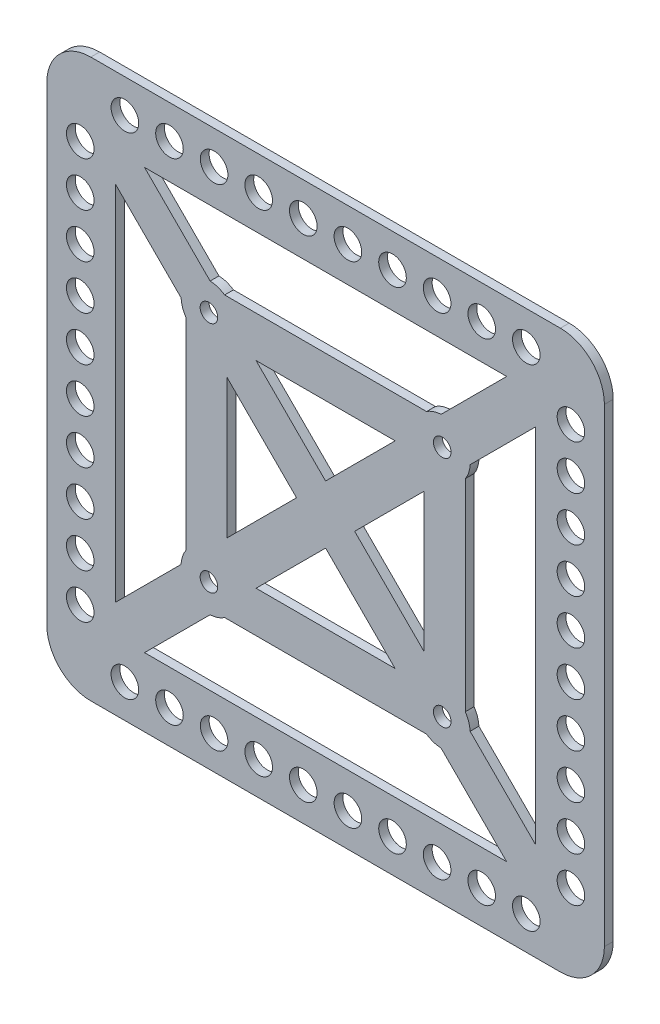
SolidWorks part; units mm, degrees
ref_plane "Front Plane" through (0, 0, 0) normal (0, 0, 1) x (1, 0, 0)
ref_plane "Top Plane" through (0, 0, 0) normal (0, 1, 0) x (1, 0, 0)
ref_plane "Right Plane" through (0, 0, 0) normal (1, 0, 0) x (0, 0, -1)
sketch "Sketch1" plane through (0, 0, 0) normal (0, 0, 1) x (1, 0, 0)
  line L0 (453.6808, -1249.6067) -> (438.4808, -1249.6067) construction
  line L1 (467.0808, -1278.2067) -> (577.0808, -1278.2067) construction
  line L2 (467.0808, -1278.2067) -> (467.0808, -1388.2067) construction
  line L3 (467.0808, -1388.2067) -> (577.0808, -1388.2067) construction
  line L4 (577.0808, -1278.2067) -> (577.0808, -1388.2067) construction
  line L5 (438.4808, -1264.8067) -> (438.4808, -1401.6067) construction
  line L6 (453.6808, -1249.6067) -> (590.4808, -1249.6067) construction
  line L7 (467.0808, -1388.2067) -> (577.0808, -1278.2067) construction
  line L8 (605.6808, -1401.6067) -> (605.6808, -1264.8067) construction
  line L9 (590.4808, -1416.8067) -> (453.6808, -1416.8067) construction
  line L10 (605.6808, -1401.6067) -> (605.6808, -1416.8067) construction
  line L12 (427.0808, -1238.2067) -> (617.0808, -1238.2067) construction
  line L13 (427.0808, -1238.2067) -> (427.0808, -1428.2067) construction
  line L14 (427.0808, -1428.2067) -> (617.0808, -1428.2067) construction
  line L15 (617.0808, -1238.2067) -> (617.0808, -1428.2067) construction
  line L16 (427.0808, -1238.2067) -> (617.0808, -1428.2067) construction
  line L17 (427.0808, -1428.2067) -> (617.0808, -1238.2067) construction
  circle A0 centre (453.6808, -1249.6067) radius 4.7
  circle A1 centre (453.6808, -1249.6067) radius 5.7
  circle A2 centre (468.8808, -1249.6067) radius 4.7
  circle A3 centre (468.8808, -1249.6067) radius 5.7
  circle A4 centre (484.0808, -1249.6067) radius 4.7
  circle A5 centre (484.0808, -1249.6067) radius 5.7
  circle A6 centre (499.2808, -1249.6067) radius 4.7
  circle A7 centre (499.2808, -1249.6067) radius 5.7
  circle A8 centre (514.4808, -1249.6067) radius 4.7
  circle A9 centre (514.4808, -1249.6067) radius 5.7
  circle A10 centre (529.6808, -1249.6067) radius 4.7
  circle A11 centre (529.6808, -1249.6067) radius 5.7
  circle A12 centre (544.8808, -1249.6067) radius 4.7
  circle A13 centre (544.8808, -1249.6067) radius 5.7
  circle A14 centre (560.0808, -1249.6067) radius 4.7
  circle A15 centre (560.0808, -1249.6067) radius 5.7
  circle A16 centre (575.2808, -1249.6067) radius 4.7
  circle A17 centre (575.2808, -1249.6067) radius 5.7
  circle A18 centre (590.4808, -1249.6067) radius 4.7
  circle A19 centre (590.4808, -1249.6067) radius 5.7
  circle A20 centre (438.4808, -1249.6067) radius 4.7 construction
  circle A21 centre (438.4808, -1249.6067) radius 5.7 construction
  circle A22 centre (438.4808, -1264.8067) radius 4.7
  circle A23 centre (438.4808, -1264.8067) radius 5.7
  circle A24 centre (438.4808, -1280.0067) radius 4.7
  circle A25 centre (438.4808, -1280.0067) radius 5.7
  circle A26 centre (438.4808, -1295.2067) radius 4.7
  circle A27 centre (438.4808, -1295.2067) radius 5.7
  circle A28 centre (438.4808, -1310.4067) radius 4.7
  circle A29 centre (438.4808, -1310.4067) radius 5.7
  circle A30 centre (438.4808, -1325.6067) radius 4.7
  circle A31 centre (438.4808, -1325.6067) radius 5.7
  circle A32 centre (438.4808, -1340.8067) radius 4.7
  circle A33 centre (438.4808, -1340.8067) radius 5.7
  circle A34 centre (438.4808, -1356.0067) radius 4.7
  circle A35 centre (438.4808, -1356.0067) radius 5.7
  circle A36 centre (438.4808, -1371.2067) radius 4.7
  circle A37 centre (438.4808, -1371.2067) radius 5.7
  circle A38 centre (438.4808, -1386.4067) radius 4.7
  circle A39 centre (438.4808, -1386.4067) radius 5.7
  circle A40 centre (438.4808, -1401.6067) radius 4.7
  circle A41 centre (438.4808, -1401.6067) radius 5.7
  circle A42 centre (605.6808, -1416.8067) radius 5.7 construction
  circle A43 centre (605.6808, -1416.8067) radius 4.7 construction
  circle A44 centre (453.6808, -1416.8067) radius 5.7
  circle A45 centre (453.6808, -1416.8067) radius 4.7
  circle A46 centre (468.8808, -1416.8067) radius 5.7
  circle A47 centre (468.8808, -1416.8067) radius 4.7
  circle A48 centre (484.0808, -1416.8067) radius 5.7
  circle A49 centre (484.0808, -1416.8067) radius 4.7
  circle A50 centre (499.2808, -1416.8067) radius 5.7
  circle A51 centre (499.2808, -1416.8067) radius 4.7
  circle A52 centre (514.4808, -1416.8067) radius 5.7
  circle A53 centre (514.4808, -1416.8067) radius 4.7
  circle A54 centre (529.6808, -1416.8067) radius 5.7
  circle A55 centre (529.6808, -1416.8067) radius 4.7
  circle A56 centre (544.8808, -1416.8067) radius 5.7
  circle A57 centre (544.8808, -1416.8067) radius 4.7
  circle A58 centre (560.0808, -1416.8067) radius 5.7
  circle A59 centre (560.0808, -1416.8067) radius 4.7
  circle A60 centre (575.2808, -1416.8067) radius 5.7
  circle A61 centre (575.2808, -1416.8067) radius 4.7
  circle A62 centre (590.4808, -1416.8067) radius 5.7
  circle A63 centre (590.4808, -1416.8067) radius 4.7
  circle A64 centre (605.6808, -1264.8067) radius 5.7
  circle A65 centre (605.6808, -1264.8067) radius 4.7
  circle A66 centre (605.6808, -1280.0067) radius 5.7
  circle A67 centre (605.6808, -1280.0067) radius 4.7
  circle A68 centre (605.6808, -1295.2067) radius 5.7
  circle A69 centre (605.6808, -1295.2067) radius 4.7
  circle A70 centre (605.6808, -1310.4067) radius 5.7
  circle A71 centre (605.6808, -1310.4067) radius 4.7
  circle A72 centre (605.6808, -1325.6067) radius 5.7
  circle A73 centre (605.6808, -1325.6067) radius 4.7
  circle A74 centre (605.6808, -1340.8067) radius 5.7
  circle A75 centre (605.6808, -1340.8067) radius 4.7
  circle A76 centre (605.6808, -1356.0067) radius 5.7
  circle A77 centre (605.6808, -1356.0067) radius 4.7
  circle A78 centre (605.6808, -1371.2067) radius 5.7
  circle A79 centre (605.6808, -1371.2067) radius 4.7
  circle A80 centre (605.6808, -1386.4067) radius 5.7
  circle A81 centre (605.6808, -1386.4067) radius 4.7
  circle A82 centre (605.6808, -1401.6067) radius 5.7
  circle A83 centre (605.6808, -1401.6067) radius 4.7
  point P4 (522.0808, -1249.6067)
  point P5 (522.0808, -1278.2067)
  point P10 (438.4808, -1333.2067)
  point P42 (467.0808, -1333.2067)
  point P136 (522.0808, -1333.2067)
  dimension "D5" = 9.4
  dimension "D6" = 1
  dimension "D1" = 110
  dimension "D2" = 110
  dimension "D3" = 190
  dimension "D4" = 136.8
  dimension "D8" = 11
  dimension "D9" = 136.8
  dimension "D10" = 190
  dimension "D7" = 10
extrude "Boss-Extrude1" add sketch "Sketch1" along normal blind 16
sketch "Sketch4" plane through (0, 0, 0) normal (0, 0, 1) x (1, 0, 0)
  line L0 (427.0808, -1238.2067) -> (617.0808, -1428.2067) construction
  line L1 (427.0808, -1428.2067) -> (617.0808, -1428.2067)
  line L2 (427.0808, -1428.2067) -> (427.0808, -1238.2067)
  line L3 (427.0808, -1238.2067) -> (617.0808, -1238.2067)
  line L4 (617.0808, -1428.2067) -> (617.0808, -1238.2067)
  line L5 (427.0808, -1428.2067) -> (617.0808, -1238.2067) construction
  line L6 (427.0808, -1238.2067) -> (617.0808, -1428.2067) construction
  circle A0 centre (438.4808, -1264.8067) radius 4.7 construction
  circle A1 centre (438.4808, -1280.0067) radius 4.7 construction
  circle A2 centre (438.4808, -1295.2067) radius 4.7 construction
  circle A3 centre (438.4808, -1310.4067) radius 4.7 construction
  circle A4 centre (438.4808, -1325.6067) radius 4.7 construction
  circle A5 centre (438.4808, -1340.8067) radius 4.7 construction
  circle A6 centre (438.4808, -1356.0067) radius 4.7 construction
  circle A7 centre (438.4808, -1371.2067) radius 4.7 construction
  circle A8 centre (438.4808, -1386.4067) radius 4.7 construction
  circle A9 centre (438.4808, -1401.6067) radius 4.7 construction
  circle A10 centre (453.6808, -1416.8067) radius 4.7 construction
  circle A11 centre (468.8808, -1416.8067) radius 4.7 construction
  circle A12 centre (484.0808, -1416.8067) radius 4.7 construction
  circle A13 centre (499.2808, -1416.8067) radius 4.7 construction
  circle A14 centre (514.4808, -1416.8067) radius 4.7 construction
  circle A15 centre (529.6808, -1416.8067) radius 4.7 construction
  circle A16 centre (544.8808, -1416.8067) radius 4.7 construction
  circle A17 centre (560.0808, -1416.8067) radius 4.7 construction
  circle A18 centre (575.2808, -1416.8067) radius 4.7 construction
  circle A19 centre (590.4808, -1416.8067) radius 4.7 construction
  circle A20 centre (605.6808, -1401.6067) radius 4.7 construction
  circle A21 centre (605.6808, -1386.4067) radius 4.7 construction
  circle A22 centre (605.6808, -1371.2067) radius 4.7 construction
  circle A23 centre (605.6808, -1356.0067) radius 4.7 construction
  circle A24 centre (605.6808, -1340.8067) radius 4.7 construction
  circle A25 centre (605.6808, -1325.6067) radius 4.7 construction
  circle A26 centre (605.6808, -1310.4067) radius 4.7 construction
  circle A27 centre (605.6808, -1295.2067) radius 4.7 construction
  circle A28 centre (605.6808, -1280.0067) radius 4.7 construction
  circle A29 centre (605.6808, -1264.8067) radius 4.7 construction
  circle A30 centre (590.4808, -1249.6067) radius 4.7 construction
  circle A31 centre (575.2808, -1249.6067) radius 4.7 construction
  circle A32 centre (560.0808, -1249.6067) radius 4.7 construction
  circle A33 centre (544.8808, -1249.6067) radius 4.7 construction
  circle A34 centre (529.6808, -1249.6067) radius 4.7 construction
  circle A35 centre (514.4808, -1249.6067) radius 4.7 construction
  circle A36 centre (499.2808, -1249.6067) radius 4.7 construction
  circle A37 centre (484.0808, -1249.6067) radius 4.7 construction
  circle A38 centre (468.8808, -1249.6067) radius 4.7 construction
  circle A39 centre (453.6808, -1249.6067) radius 4.7 construction
  circle A40 centre (438.4808, -1264.8067) radius 4.7
  circle A41 centre (438.4808, -1280.0067) radius 4.7
  circle A42 centre (438.4808, -1295.2067) radius 4.7
  circle A43 centre (438.4808, -1310.4067) radius 4.7
  circle A44 centre (438.4808, -1325.6067) radius 4.7
  circle A45 centre (438.4808, -1340.8067) radius 4.7
  circle A46 centre (438.4808, -1356.0067) radius 4.7
  circle A47 centre (438.4808, -1371.2067) radius 4.7
  circle A48 centre (438.4808, -1386.4067) radius 4.7
  circle A49 centre (438.4808, -1401.6067) radius 4.7
  circle A50 centre (453.6808, -1416.8067) radius 4.7
  circle A51 centre (468.8808, -1416.8067) radius 4.7
  circle A52 centre (484.0808, -1416.8067) radius 4.7
  circle A53 centre (499.2808, -1416.8067) radius 4.7
  circle A54 centre (514.4808, -1416.8067) radius 4.7
  circle A55 centre (529.6808, -1416.8067) radius 4.7
  circle A56 centre (544.8808, -1416.8067) radius 4.7
  circle A57 centre (560.0808, -1416.8067) radius 4.7
  circle A58 centre (575.2808, -1416.8067) radius 4.7
  circle A59 centre (590.4808, -1416.8067) radius 4.7
  circle A60 centre (605.6808, -1401.6067) radius 4.7
  circle A61 centre (605.6808, -1386.4067) radius 4.7
  circle A62 centre (605.6808, -1371.2067) radius 4.7
  circle A63 centre (605.6808, -1356.0067) radius 4.7
  circle A64 centre (605.6808, -1340.8067) radius 4.7
  circle A65 centre (605.6808, -1325.6067) radius 4.7
  circle A66 centre (605.6808, -1310.4067) radius 4.7
  circle A67 centre (605.6808, -1295.2067) radius 4.7
  circle A68 centre (605.6808, -1280.0067) radius 4.7
  circle A69 centre (605.6808, -1264.8067) radius 4.7
  circle A70 centre (590.4808, -1249.6067) radius 4.7
  circle A71 centre (575.2808, -1249.6067) radius 4.7
  circle A72 centre (560.0808, -1249.6067) radius 4.7
  circle A73 centre (544.8808, -1249.6067) radius 4.7
  circle A74 centre (529.6808, -1249.6067) radius 4.7
  circle A75 centre (514.4808, -1249.6067) radius 4.7
  circle A76 centre (499.2808, -1249.6067) radius 4.7
  circle A77 centre (484.0808, -1249.6067) radius 4.7
  circle A78 centre (468.8808, -1249.6067) radius 4.7
  circle A79 centre (453.6808, -1249.6067) radius 4.7
  point P0 (522.0808, -1333.2067)
extrude "Boss-Extrude3" add sketch "Sketch4" against normal blind 6
sketch "Sketch5" plane through (0, 0, 0) normal (0, 0, 1) x (1, 0, 0)
  circle A0 centre (482.3308, -1293.4567) radius 3
  circle A1 centre (561.8308, -1293.4567) radius 3
  circle A2 centre (561.8308, -1372.9567) radius 3
  circle A3 centre (482.3308, -1372.9567) radius 3
  point P11 (522.0808, -1333.2067)
  dimension "D1" = 6
  dimension "D2" = 4
extrude "Cut-Extrude1" cut sketch "Sketch5" against normal blind 6
sketch "Sketch7" plane through (0, 0, -6) normal (0, 0, -1) x (-1, 0, 0)
  line L6 (-617.0808, -1238.2067) -> (-427.0808, -1428.2067) construction
  line L7 (-617.0808, -1428.2067) -> (-427.0808, -1238.2067) construction
  line L8 (-612.1311, -1433.1565) -> (-422.1311, -1243.1565)
  line L9 (-450.4808, -1404.8067) -> (-593.6808, -1404.8067)
  line L10 (-450.4808, -1404.8067) -> (-450.4808, -1261.6067)
  line L11 (-450.4808, -1261.6067) -> (-593.6808, -1261.6067)
  line L12 (-593.6808, -1404.8067) -> (-593.6808, -1261.6067)
  line L13 (-450.4808, -1404.8067) -> (-593.6808, -1261.6067) construction
  line L14 (-450.4808, -1261.6067) -> (-593.6808, -1404.8067) construction
  line L15 (-474.4808, -1380.8067) -> (-569.6808, -1380.8067)
  line L16 (-474.4808, -1380.8067) -> (-474.4808, -1285.6067)
  line L17 (-474.4808, -1285.6067) -> (-569.6808, -1285.6067)
  line L18 (-569.6808, -1380.8067) -> (-569.6808, -1285.6067)
  line L19 (-474.4808, -1380.8067) -> (-569.6808, -1285.6067) construction
  line L20 (-474.4808, -1285.6067) -> (-569.6808, -1380.8067) construction
  line L21 (-622.0306, -1243.1565) -> (-432.0306, -1433.1565)
  line L22 (-622.0306, -1423.257) -> (-432.0306, -1233.257)
  line L23 (-612.1311, -1233.257) -> (-422.1311, -1423.257)
  line L24 (-467.0808, -1388.2067) -> (-577.0808, -1278.2067) construction
  line L26 (-488.4808, -1366.8067) -> (-555.6808, -1366.8067)
  line L27 (-488.4808, -1366.8067) -> (-488.4808, -1299.6067)
  line L28 (-488.4808, -1299.6067) -> (-555.6808, -1299.6067)
  line L29 (-555.6808, -1366.8067) -> (-555.6808, -1299.6067)
  line L30 (-488.4808, -1366.8067) -> (-555.6808, -1299.6067) construction
  line L31 (-488.4808, -1299.6067) -> (-555.6808, -1366.8067) construction
  circle A0 centre (-605.6808, -1401.6067) radius 5.7 construction
  point P4 (-522.0808, -1333.2067)
  point P18 (-522.0808, -1333.2067)
  point P37 (-522.0808, -1333.2067)
  dimension "D1" = 12
  dimension "D2" = 12
  dimension "D3" = 12
  dimension "D6" = 14
  dimension "D7" = 24
  dimension "D4" = 7
  dimension "D5" = 7
extrude "Cut-Extrude2" cut sketch "Sketch7" against normal blind 6 contours L11 L23 L17 L22 | L22 L28 L23 | L29 L22 L21 | L26 L21 L8 | L23 L27 L8 | L16 L23 L10 L8 | L21 L15 L8 L9 | L12 L22 L18 L21 region at (522.0808, -1393.7725, -6) region at (522.0808, -1358.9066, -6) region at (582.6466, -1333.2067, -6) region at (461.5151, -1333.2067, -6) region at (496.381, -1333.2067, -6) region at (547.7807, -1333.2067, -6) region at (522.0808, -1307.5069, -6) region at (522.0808, -1272.641, -6)
sketch "Sketch8" plane through (0, 0, 0) normal (0, 0, 1) x (1, 0, 0)
  circle A0 centre (482.3308, -1372.9567) radius 9.5
  circle A1 centre (561.8308, -1372.9567) radius 9.5
  circle A2 centre (561.8308, -1293.4567) radius 9.5
  circle A3 centre (482.3308, -1293.4567) radius 9.5
  circle A4 centre (482.3308, -1293.4567) radius 3
  circle A5 centre (561.8308, -1293.4567) radius 3.1094
  circle A6 centre (561.8308, -1372.9567) radius 3
  circle A7 centre (482.3308, -1372.9567) radius 3
  dimension "D1" = 19
  dimension "D2" = 19
  dimension "D3" = 19
  dimension "D4" = 19
extrude "Boss-Extrude4" add sketch "Sketch8" against normal blind 6
fillet "Fillet1" radius 15 4 edges at (617.0808, -1428.2067, -3) (427.0808, -1428.2067, -3) (427.0808, -1238.2067, -3) (617.0808, -1238.2067, -3)
sketch "Sketch9" plane through (0, -1238.2067, 0) normal (0, 1, 0) x (1, 0, 0)
  line L1 (432.7808, 0) -> (611.3808, 0)
  line L2 (432.7808, 0) -> (432.7808, -16)
  line L3 (432.7808, -16) -> (611.3808, -16)
  line L4 (611.3808, 0) -> (611.3808, -16)
  line L5 (432.7808, 0) -> (611.3808, -16) construction
  line L6 (432.7808, -16) -> (611.3808, 0) construction
  point P4 (522.0808, -8)
extrude "Cut-Extrude3" cut sketch "Sketch9" against normal through all
sketch "Sketch10" plane through (0, 0, 0) normal (0, 0, 1) x (1, 0, 0)
  line L4 (602.0808, -1238.2067) -> (442.0808, -1238.2067)
  line L5 (427.0808, -1253.2067) -> (427.0808, -1413.2067)
  line L6 (442.0808, -1428.2067) -> (602.0808, -1428.2067)
  line L7 (617.0808, -1413.2067) -> (617.0808, -1253.2067)
  line L8 (602.0808, -1238.2067) -> (442.0808, -1238.2067)
  line L9 (427.0808, -1253.2067) -> (427.0808, -1413.2067)
  line L10 (442.0808, -1428.2067) -> (602.0808, -1428.2067)
  line L11 (617.0808, -1413.2067) -> (617.0808, -1253.2067)
  arc A4 (617.0808, -1253.2067) -> (602.0808, -1238.2067) centre (602.0808, -1253.2067) ccw
  arc A5 (442.0808, -1238.2067) -> (427.0808, -1253.2067) centre (442.0808, -1253.2067) ccw
  arc A6 (427.0808, -1413.2067) -> (442.0808, -1428.2067) centre (442.0808, -1413.2067) ccw
  arc A7 (602.0808, -1428.2067) -> (617.0808, -1413.2067) centre (602.0808, -1413.2067) ccw
  arc A8 (617.0808, -1253.2067) -> (602.0808, -1238.2067) centre (602.0808, -1253.2067) ccw
  arc A9 (442.0808, -1238.2067) -> (427.0808, -1253.2067) centre (442.0808, -1253.2067) ccw
  arc A10 (427.0808, -1413.2067) -> (442.0808, -1428.2067) centre (442.0808, -1413.2067) ccw
  arc A11 (602.0808, -1428.2067) -> (617.0808, -1413.2067) centre (602.0808, -1413.2067) ccw
  dimension "D1" = 0
extrude "Cut-Extrude4" cut sketch "Sketch10" against normal blind 3
